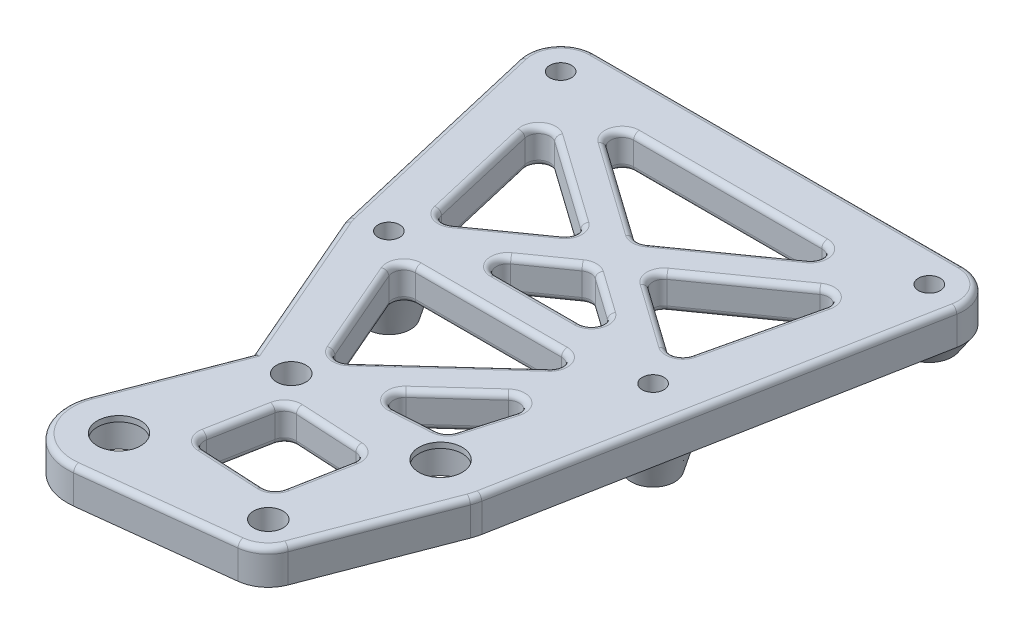
SolidWorks part; units mm, degrees
ref_plane "Front Plane" through (0, 0, 0) normal (0, 0, 1) x (1, 0, 0)
ref_plane "Top Plane" through (0, 0, 0) normal (0, 1, 0) x (1, 0, 0)
ref_plane "Right Plane" through (0, 0, 0) normal (1, 0, 0) x (0, 0, -1)
sketch "Sketch1" plane through (0, 0, 0) normal (0, 1, 0) x (1, 0, 0)
  line L0 (0, 0) -> (20.6375, 0) construction
  line L1 (20.6375, 0) -> (25.4, 19.05) construction
  line L2 (25.4, 19.05) -> (4.7625, 19.05) construction
  line L3 (4.7625, 19.05) -> (0, 0) construction
  line L8 (0.3164, 20.7568) -> (-6.6692, 2.5603)
  line L9 (4.213, 23.7807) -> (24.5757, 26.146)
  line L10 (32.0692, 16.4897) -> (25.0836, -1.7068)
  line L11 (0.8243, -7.096) -> (21.187, -4.7307)
  line L12 (0, 0) -> (25.4, 19.05) construction
  line L13 (4.7625, 19.05) -> (20.6375, 0) construction
  line L14 (7.5279, 4.1904) -> (16.2024, 3.7319)
  line L15 (17.8461, 5.0227) -> (19.3482, 12.9798)
  line L16 (17.8721, 14.8596) -> (9.1976, 15.3181)
  line L17 (7.5539, 14.0273) -> (6.0518, 6.0702)
  circle A0 centre (0, 0) radius 4.05
  circle A1 centre (25.4, 19.05) radius 4.05
  circle A2 centre (20.6375, 0) radius 2.032
  circle A3 centre (4.7625, 19.05) radius 2.032
  arc A4 (-6.6692, 2.5603) -> (0.8243, -7.096) centre (0, 0) ccw
  arc A5 (4.213, 23.7807) -> (0.3164, 20.7568) centre (4.7625, 19.05) ccw
  arc A6 (32.0692, 16.4897) -> (24.5757, 26.146) centre (25.4, 19.05) ccw
  arc A7 (21.187, -4.7307) -> (25.0836, -1.7068) centre (20.6375, 0) ccw
  arc A8 (7.5279, 4.1904) -> (6.0518, 6.0702) centre (7.6117, 5.7757) cw
  arc A9 (16.2024, 3.7319) -> (17.8461, 5.0227) centre (16.2862, 5.3172) ccw
  arc A10 (19.3482, 12.9798) -> (17.8721, 14.8596) centre (17.7883, 13.2743) ccw
  arc A11 (9.1976, 15.3181) -> (7.5539, 14.0273) centre (9.1138, 13.7328) ccw
  point P25 (5.715, 4.2863)
  point P28 (17.5886, 3.6587)
  point P31 (19.685, 14.7637)
  point P34 (7.8114, 15.3913)
  dimension "D4" = 8.1
  dimension "D5" = 4.064
  dimension "D6" = 7.1437
  dimension "D7" = 4.7625
  dimension "D12" = 1.5875
  dimension "D1" = 20.6375
  dimension "D2" = 19.05
  dimension "D3" = 4.7625
  dimension "D8" = 7.1437
  dimension "D9" = 7.1437
  dimension "D10" = 4.7625
  dimension "D11" = 4.7625
extrude "Boss-Extrude1" add sketch "Sketch1" along normal blind 4.7625
sketch "Sketch2" plane through (0, 4.7625, 0) normal (0, 1, 0) x (1, 0, 0)
  circle A0 centre (25.4, 19.05) radius 4.05 construction
  circle A1 centre (0, 0) radius 4.05 construction
  circle A2 centre (25.4, 19.05) radius 4.05
  circle A3 centre (0, 0) radius 4.05
  circle A4 centre (25.4, 19.05) radius 3
  circle A5 centre (0, 0) radius 3
  dimension "D1" = 6
extrude "Boss-Extrude2" add sketch "Sketch2" against normal blind 0.7625
sketch "Sketch3" plane through (0, 4.7625, 0) normal (0, 1, 0) x (1, 0, 0)
  line L0 (0, 0) -> (25.4, 19.05) construction
  line L1 (12.7, 9.525) -> (12.7, 24.7665) construction
  line L2 (24.5757, 26.146) -> (4.213, 23.7807) construction
  line L4 (-12.7775, 78.5812) -> (38.1775, 78.5812)
  line L5 (42.8571, 72.9341) -> (32.4194, 17.723)
  line L6 (0.3164, 20.7568) -> (-6.6692, 2.5603) construction
  line L7 (0.3164, 20.7568) -> (-0.3807, 18.941)
  line L8 (24.5757, 26.146) -> (4.213, 23.7807)
  line L9 (-0.3807, 18.941) -> (-9.9261, 40.9689)
  line L10 (-10.1942, 41.7806) -> (-17.4155, 72.7368)
  circle A0 centre (30.9562, 42.8625) radius 1.5
  circle A1 centre (25.4, 19.05) radius 3 construction
  circle A2 centre (-5.5563, 42.8625) radius 1.5
  circle A3 centre (-12.7775, 73.8187) radius 1.5
  circle A5 centre (38.1775, 73.8187) radius 1.5
  arc A6 (-12.7775, 78.5812) -> (-17.4155, 72.7368) centre (-12.7775, 73.8187) ccw
  arc A7 (42.8571, 72.9341) -> (38.1775, 78.5812) centre (38.1775, 73.8187) ccw
  arc A8 (21.187, -4.7307) -> (25.0836, -1.7068) centre (20.6375, 0) ccw construction
  arc A10 (32.0692, 16.4897) -> (24.5757, 26.146) centre (25.4, 19.05) ccw construction
  arc A14 (32.4194, 17.723) -> (24.5757, 26.146) centre (25.4, 19.05) ccw
  arc A15 (4.213, 23.7807) -> (0.3164, 20.7568) centre (4.7625, 19.05) ccw
  arc A16 (-10.1942, 41.7806) -> (-9.9261, 40.9689) centre (-5.5563, 42.8625) ccw
  dimension "D1" = 23.8125
  dimension "D2" = 5.5562
  dimension "D3" = 3
  dimension "D4" = 30.9562
  dimension "D5" = 7.2212
extrude "Boss-Extrude3" add sketch "Sketch3" against normal blind 4.7625
sketch "Sketch4" plane through (0, 4.7625, 0) normal (0, 1, 0) x (1, 0, 0)
  line L0 (-5.5563, 42.8625) -> (30.9562, 42.8625) construction
  line L1 (30.9562, 42.8625) -> (24.4148, 20.2948) construction
  line L2 (24.4148, 20.2948) -> (4.7625, 19.05) construction
  line L3 (4.7625, 19.05) -> (-5.5563, 42.8625) construction
  line L4 (4.7625, 19.05) -> (30.9562, 42.8625) construction
  line L5 (7.266, 24.544) -> (21.7585, 37.7191)
  line L6 (0.4889, 40.4812) -> (20.6907, 40.4812)
  line L7 (4.7415, 25.0875) -> (-0.9677, 38.2625)
  line L8 (5.6239, 23.0512) -> (24.7969, 40.4812) construction
  line L9 (5.6239, 23.0512) -> (-1.9292, 40.4812) construction
  line L10 (-1.9292, 40.4812) -> (24.7969, 40.4812) construction
  line L11 (14.7385, 24.9009) -> (22.1669, 31.654)
  line L12 (24.7595, 30.0374) -> (22.9044, 23.6373)
  line L13 (21.48, 22.4949) -> (15.9067, 22.1419)
  line L14 (11.3888, 21.8557) -> (26.3234, 35.4326) construction
  line L15 (22.5937, 22.5655) -> (11.3888, 21.8557) construction
  line L16 (26.3234, 35.4326) -> (22.5937, 22.5655) construction
  line L17 (-5.5563, 42.8625) -> (-12.7775, 73.8187) construction
  line L18 (-12.7775, 73.8187) -> (38.1775, 73.8187) construction
  line L19 (38.1775, 73.8187) -> (30.9562, 42.8625) construction
  line L20 (12.7, 55.7849) -> (38.1775, 73.8187) construction
  line L21 (12.7, 55.7849) -> (-12.7775, 73.8187) construction
  line L22 (-5.5563, 42.8625) -> (12.7, 55.7849) construction
  line L23 (12.7, 55.7849) -> (30.9562, 42.8625) construction
  line L31 (6.7478, 57.0807) -> (-5.6204, 65.8353)
  line L32 (-4.578, 49.151) -> (-8.0836, 64.1789)
  line L33 (-2.1148, 48.2159) -> (6.7478, 54.4892)
  line L34 (-0.3012, 71.4375) -> (25.7012, 71.4375)
  line L35 (13.6172, 59.3515) -> (26.6184, 68.5543)
  line L36 (11.7828, 59.3515) -> (-1.2184, 68.5543)
  line L37 (6.0028, 48.127) -> (11.7828, 52.2183)
  line L38 (13.6172, 52.2183) -> (19.3972, 48.127)
  line L39 (6.92, 45.2437) -> (18.48, 45.2437)
  line L40 (18.6522, 57.0807) -> (31.0204, 65.8353)
  line L41 (33.4836, 64.1789) -> (29.978, 49.151)
  line L42 (18.6522, 54.4892) -> (27.5148, 48.2159)
  line L43 (1.9295, 45.2437) -> (12.7, 52.8675) construction
  line L44 (1.9295, 45.2437) -> (23.4705, 45.2437) construction
  line L45 (12.7, 52.8675) -> (23.4705, 45.2437) construction
  line L46 (34.4335, 68.2512) -> (29.4417, 46.852) construction
  line L47 (16.8216, 55.7849) -> (29.4417, 46.852) construction
  line L48 (16.8216, 55.7849) -> (34.4335, 68.2512) construction
  line L49 (-5.2917, 71.4375) -> (30.6917, 71.4375) construction
  line L50 (12.7, 58.7023) -> (30.6917, 71.4375) construction
  line L51 (12.7, 58.7023) -> (-5.2917, 71.4375) construction
  line L52 (8.5784, 55.7849) -> (-9.0335, 68.2512) construction
  line L53 (-4.0417, 46.852) -> (8.5784, 55.7849) construction
  line L54 (-4.0417, 46.852) -> (-9.0335, 68.2512) construction
  line L55 (25.4, 19.05) -> (24.4148, 20.2948) construction
  line L56 (4.7625, 19.05) -> (25.4, 19.05) construction
  arc A0 (7.266, 24.544) -> (4.7415, 25.0875) centre (6.1981, 25.7187) cw
  arc A1 (21.7585, 37.7191) -> (20.6907, 40.4812) centre (20.6907, 38.8937) ccw
  arc A2 (0.4889, 40.4812) -> (-0.9677, 38.2625) centre (0.4889, 38.8937) ccw
  arc A3 (14.7385, 24.9009) -> (15.9067, 22.1419) centre (15.8063, 23.7262) ccw
  arc A4 (22.1669, 31.654) -> (24.7595, 30.0374) centre (23.2348, 30.4794) cw
  arc A5 (22.9044, 23.6373) -> (21.48, 22.4949) centre (21.3796, 24.0793) cw
  arc A12 (6.0028, 48.127) -> (6.92, 45.2437) centre (6.92, 46.8312) ccw
  arc A13 (11.7828, 52.2183) -> (13.6172, 52.2183) centre (12.7, 50.9225) cw
  arc A14 (19.3972, 48.127) -> (18.48, 45.2437) centre (18.48, 46.8312) cw
  arc A15 (29.978, 49.151) -> (27.5148, 48.2159) centre (28.432, 49.5116) cw
  arc A16 (18.6522, 57.0807) -> (18.6522, 54.4892) centre (19.5694, 55.7849) ccw
  arc A17 (31.0204, 65.8353) -> (33.4836, 64.1789) centre (31.9376, 64.5396) cw
  arc A18 (25.7012, 71.4375) -> (26.6184, 68.5543) centre (25.7012, 69.85) cw
  arc A19 (13.6172, 59.3515) -> (11.7828, 59.3515) centre (12.7, 60.6473) cw
  arc A20 (-0.3012, 71.4375) -> (-1.2184, 68.5543) centre (-0.3012, 69.85) ccw
  arc A21 (6.7478, 57.0807) -> (6.7478, 54.4892) centre (5.8306, 55.7849) cw
  arc A22 (-4.578, 49.151) -> (-2.1148, 48.2159) centre (-3.032, 49.5116) ccw
  arc A23 (-5.6204, 65.8353) -> (-8.0836, 64.1789) centre (-6.5376, 64.5396) ccw
  dimension "D2" = 1.5875
  dimension "D4" = 1.5875
  dimension "D5" = 1.5875
  dimension "D10" = 1.5875
  dimension "D11" = 51.64
  dimension "D1" = 2.3813
  dimension "D3" = 2.3813
  dimension "D6" = 2.3813
  dimension "D7" = 2.3813
  dimension "D8" = 2.3813
  dimension "D9" = 2.3813
extrude "Cut-Extrude1" cut sketch "Sketch4" against normal through all
sketch "Sketch5" plane through (0, 0, 0) normal (0, -1, 0) x (1, 0, 0)
  circle A0 centre (-5.5563, -42.8625) radius 3
  circle A1 centre (-5.5563, -42.8625) radius 1.5 construction
  circle A2 centre (-5.5563, -42.8625) radius 1.5
  circle A3 centre (30.9562, -42.8625) radius 1.5 construction
  circle A4 centre (30.9562, -42.8625) radius 1.5
  circle A5 centre (30.9562, -42.8625) radius 3
  dimension "D1" = 6
extrude "Boss-Extrude4" add sketch "Sketch5" along normal blind 5.5245
chamfer "Chamfer1" distance 1.5875 distance2 5.5245 2 edges at (30.9562, 0, -39.8625) (-5.5563, 0, -39.8625) first distance on face at (30.9562, 0, -39.8625)
sketch "Sketch6" plane through (0, 0, 0) normal (0, -1, 0) x (1, 0, 0)
  circle A0 centre (38.1775, -73.8187) radius 1.5 construction
  circle A1 centre (-12.7775, -73.8187) radius 1.5 construction
  circle A2 centre (38.1775, -73.8187) radius 1.5
  circle A3 centre (-12.7775, -73.8187) radius 1.5
  circle A4 centre (-12.7775, -73.8187) radius 3.175
  circle A5 centre (38.1775, -73.8187) radius 3.175
  dimension "D1" = 6.35
extrude "Boss-Extrude5" add sketch "Sketch6" along normal blind 2.3495
chamfer "Chamfer2" distance 1.5875 distance2 2.3495 2 edges at (38.1775, 0, -70.6437) (-12.7775, 0, -70.6437) first distance on face at (38.1775, 0, -70.6437)
fillet "Fillet1" radius 0.7937 101 edges at (-3.525, 4.7625, -10.7507) (-5.6437, 4.7625, 4.3797) (11.0056, 4.7625, 5.9134) (23.5573, 4.7625, 3.7625) (28.5764, 4.7625, -7.3914) (32.272, 4.7625, -17.0985) (-5.1534, 4.7625, -29.955) (-10.0784, 4.7625, -41.3687) (-13.8048, 4.7625, -57.2587) (-16.508, 4.7625, -76.7792) (12.7, 4.7625, -78.5812) (41.8445, 4.7625, -76.8575) (37.6382, 4.7625, -45.3285) (32.8235, 0, -65.8569) (31.7308, 0, -56.665) (28.9954, 0, -48.0275) (23.0835, 0, -51.3525) (17.9819, 0, -55.7849) (32.8235, 4.7625, -65.8569) (31.7308, 4.7625, -56.665) (28.9954, 4.7625, -48.0275) (23.0835, 4.7625, -51.3525) (17.9819, 4.7625, -55.7849) (27.214, 0, -70.3312) (20.1178, 0, -63.9529) (12.7, 0, -59.0598) (5.2822, 0, -63.9529) (-1.814, 0, -70.3312) (27.214, 4.7625, -70.3312) (20.1178, 4.7625, -63.9529) (12.7, 4.7625, -59.0598) (5.2822, 4.7625, -63.9529) (-1.814, 4.7625, -70.3312) (-7.4235, 0, -65.8569) (0.5637, 0, -61.458) (7.4181, 0, -55.7849) (2.3165, 0, -51.3525) (-3.5954, 0, -48.0275) (-7.4235, 4.7625, -65.8569) (0.5637, 4.7625, -61.458) (7.4181, 4.7625, -55.7849) (2.3165, 4.7625, -51.3525) (-3.5954, 4.7625, -48.0275) (12.7, 0, -52.51) (16.5072, 0, -50.1726) (19.9928, 0, -46.35) (12.7, 0, -45.2437) (5.4072, 0, -46.35) (12.7, 4.7625, -52.51) (16.5072, 4.7625, -50.1726) (19.9928, 4.7625, -46.35) (12.7, 4.7625, -45.2437) (5.4072, 4.7625, -46.35) (22.1713, 0, -39.4662) (14.5122, 0, -31.1316) (5.864, 0, -24.1667) (1.8869, 0, -31.675) (-0.8382, 0, -39.765) (22.1713, 4.7625, -39.4662) (14.5122, 4.7625, -31.1316) (5.864, 4.7625, -24.1667) (1.8869, 4.7625, -31.675) (-0.8382, 4.7625, -39.765) (24.0747, 0, -31.8264) (23.8319, 0, -26.8374) (22.3729, 0, -22.8408) (18.6933, 0, -22.3184) (14.3445, 0, -23.1072) (24.0747, 4.7625, -31.8264) (23.8319, 4.7625, -26.8374) (22.3729, 4.7625, -22.8408) (18.6933, 4.7625, -22.3184) (14.3445, 4.7625, -23.1072) (19.0368, 4.7625, -14.2547) (18.5972, 4.7625, -9.0013) (17.2666, 4.7625, -4.0687) (11.8652, 4.7625, -3.9612) (6.3632, 4.7625, -4.7953) (6.8028, 4.7625, -10.0487) (8.1334, 4.7625, -14.9813) (19.0368, 0, -14.2547) (18.5972, 0, -9.0013) (17.2666, 0, -4.0687) (11.8652, 0, -3.9612) (6.3632, 0, -4.7953) (6.8028, 0, -10.0487) (8.1334, 0, -14.9813) (24.8363, 0, -61.458) (24.8363, 4.7625, -61.458) (12.7, 0, -71.4375) (12.7, 4.7625, -71.4375) (-6.3308, 0, -56.665) (-6.3308, 4.7625, -56.665) (8.8928, 0, -50.1726) (8.8928, 4.7625, -50.1726) (10.5898, 0, -40.4812) (10.5898, 4.7625, -40.4812) (18.4527, 0, -28.2775) (18.4527, 4.7625, -28.2775) (13.5348, 4.7625, -15.0888) (13.5348, 0, -15.0888)
equation "\"D9@Sketch1\"=\"D8@Sketch1\""
equation "\"D11@Sketch1\"=\"D10@Sketch1\""
